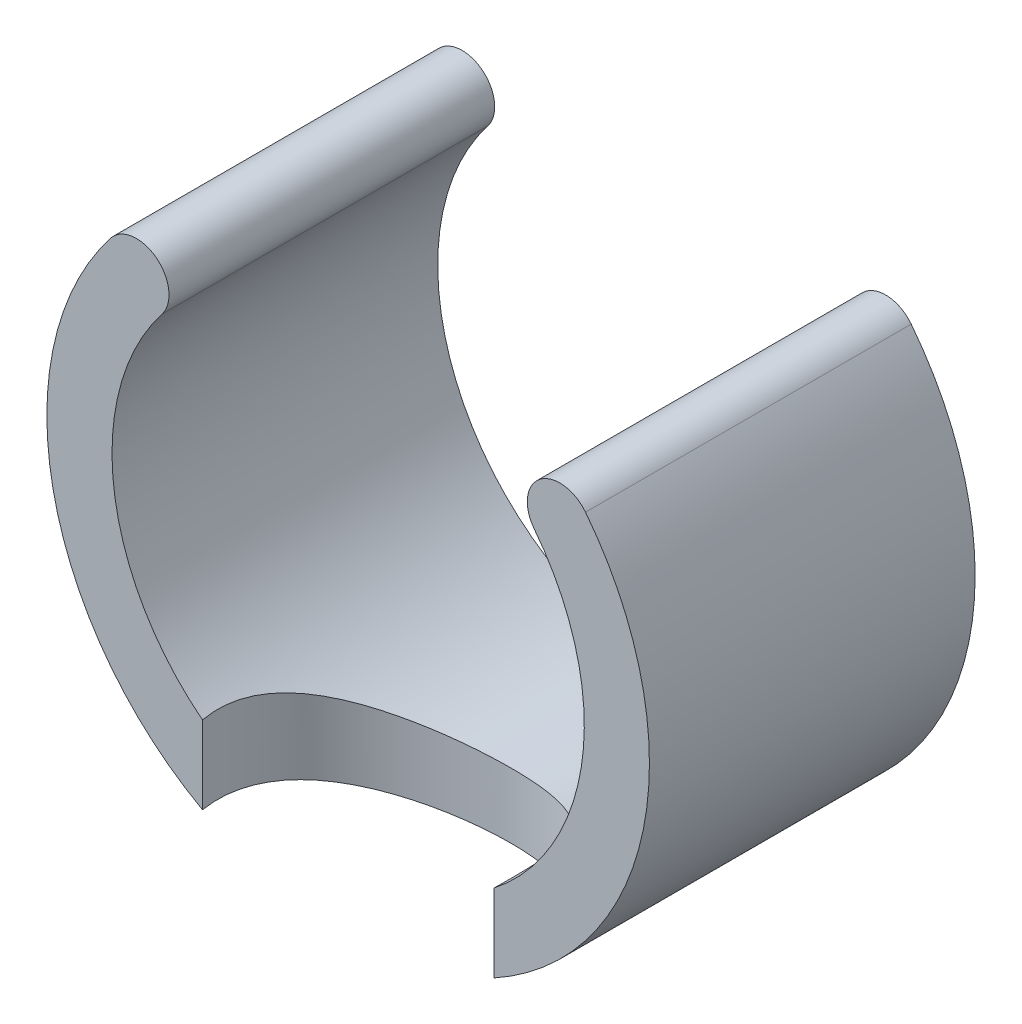
SolidWorks part; units mm, degrees
ref_plane "Спереди" through (0, 0, 0) normal (0, 0, 1) x (1, 0, 0)
ref_plane "Сверху" through (0, 0, 0) normal (0, 1, 0) x (1, 0, 0)
ref_plane "Справа" through (0, 0, 0) normal (1, 0, 0) x (0, 0, -1)
sketch "Эскиз1" plane through (0, 0, 0) normal (0, 0, 1) x (1, 0, 0)
  line L0 (0, -9.25) -> (0, 9.25) construction
  line L1 (-5.5, 5.0806) -> (-5.5, -4.3036) construction
  line L2 (5.5, 5.0806) -> (5.5, -4.3036) construction
  arc A0 (-5.7121, 4.4648) -> (5.7121, 4.4648) centre (0, 0) ccw
  arc A1 (-7.2879, 5.6964) -> (7.2879, 5.6964) centre (0, 0) ccw
  arc A2 (-7.2879, 5.6964) -> (-5.7121, 4.4648) centre (-6.5, 5.0806) cw
  arc A3 (7.2879, 5.6964) -> (5.7121, 4.4648) centre (6.5, 5.0806) ccw
  circle A5 centre (0, 0) radius 9.25 construction
  circle A6 centre (0, 0) radius 7.25 construction
  point P4 (6.9332, 2.1197)
  point P17 (8.8458, 2.7044)
  dimension "D1" = 14.5
  dimension "D3" = 11
  dimension "D2" = 2
extrude "Основа" add sketch "Эскиз1" along normal blind 10
sketch "Эскиз2" plane through (0, 0, 0) normal (1, 0, 0) x (0, 0, -1)
  line L0 (-5, -9.25) -> (-5, 7) construction
  line L1 (-10, -9.25) -> (0, -9.25) construction
  line L3 (0, -9.25) -> (0, 5.6964) construction
  line L4 (2, -5.25) -> (2, 6)
  line L5 (4, 6) -> (4, -5.25)
  line L6 (0, -9.25) -> (0, -7.25)
  line L7 (-10, -9.25) -> (0, -9.25) construction
  line L8 (-10, 5.6964) -> (-10, -9.25) construction
  arc A0 (2, -5.25) -> (0, -7.25) centre (0, -5.25) cw
  circle A1 centre (-5, 0) radius 7 construction
  arc A2 (4, -5.25) -> (0, -9.25) centre (0, -5.25) cw
  arc A3 (2.1323, -1.8657) -> (0, -9.25) centre (0, -5.25) cw construction
  arc A4 (2, 6) -> (4, 6) centre (3, 6) cw
  arc A5 (1.0661, -3.5579) -> (0, -7.25) centre (0, -5.25) cw construction
  point P29 (3, 7)
  dimension "D1" = 14
  dimension "D3" = 9.25
  dimension "D2" = 2
extrude "Бобышка-Вытянуть2" [suppressed] add sketch "Эскиз2" along normal blind 5 and the other way blind 5
sketch "Эскиз3" plane through (0, 0, 0) normal (0, 0, -1) x (-1, 0, 0)
  line L0 (-1.5, 7.0931) -> (-2.75, 0.004)
  line L1 (0, 7.25) -> (0, -9.25) construction
  line L2 (1.5, 7.0931) -> (2.75, 0.004)
  arc A0 (-6, -7.0401) -> (6, -7.0401) centre (0, 0) ccw
  arc A3 (-7.2879, 5.6964) -> (7.2879, 5.6964) centre (0, 0) ccw construction
  arc A4 (-2.75, 0.004) -> (-6, -7.0401) centre (-17.736, 2.6465) cw
  arc A5 (2.75, 0.004) -> (6, -7.0401) centre (17.736, 2.6465) ccw
  arc A6 (1.5, 7.0931) -> (-1.5, 7.0931) centre (0, 0) ccw
  arc A7 (-5.7121, 4.4648) -> (5.7121, 4.4648) centre (0, 0) ccw construction
  dimension "D1" = 10
  dimension "D2" = 3
  dimension "D3" = 12
  dimension "D4" = 5.5
extrude "упорчик снизу" [suppressed] add sketch "Эскиз3" along normal blind 2 from offset 1
fillet "Скругление1" [suppressed] radius 1
ref_plane "Плоскость1" through (0, -9.25, 0) normal (0, -1, 0) x (-1, 0, 0)
sketch "Эскиз5" plane through (0, 0, 10) normal (0, 0, 1) x (1, 0, 0)
  line L0 (0, 9.25) -> (0, -9.25) construction
  arc A1 (-5.0581, -5.194) -> (5.0581, -5.194) centre (0, 0) ccw
  arc A2 (-5.7121, 4.4648) -> (5.7121, 4.4648) centre (0, 0) ccw construction
  arc A3 (-7.5, -7.7015) -> (7.5, -7.7015) centre (0, 0) ccw
  arc A5 (-7.5, -7.7015) -> (-5.0581, -5.194) centre (-6.2791, -6.4477) cw
  arc A6 (7.5, -7.7015) -> (5.0581, -5.194) centre (6.2791, -6.4477) ccw
  dimension "D1" = 15
  dimension "D2" = 3.5
extrude "выступ под толкатель" [suppressed] add sketch "Эскиз5" along normal blind 6 and the other way blind 9
sketch "Эскиз6" plane through (0, -9.25, 0) normal (0, -1, 0) x (-1, 0, 0)
  circle A0 centre (0, -9.5) radius 4.5
  dimension "D1" = 9.5
  dimension "D2" = 9
extrude "Вырез под толкатель" cut sketch "Эскиз6" against normal through all and the other way through all
sketch "Эскиз7" [suppressed] plane through (0, 0, -3) normal (0, 0, -1) x (-1, 0, 0)
  line L0 (0, 0) -> (0, -9.25) construction
  line L1 (-7.0595, -8.8662) -> (-5.2044, -7.647)
  line L2 (-1.3246, -11.2557) -> (-1.7652, -9.08)
  line L3 (-5, -12) -> (-3.5577, -8.5385) construction
  line L4 (5, -12) -> (3.5577, -8.5385) construction
  line L5 (1.3246, -11.2557) -> (1.7652, -9.08)
  line L6 (7.0595, -8.8662) -> (5.2044, -7.647)
  arc A0 (-7.0595, -8.8662) -> (-1.3246, -11.2557) centre (-5, -12) ccw
  arc A1 (-5.2044, -7.647) -> (5.2044, -7.647) centre (0, 0) ccw construction
  circle A2 centre (-5, -12) radius 1.4
  arc A11 (-5.2044, -7.647) -> (-1.7652, -9.08) centre (0, 0) ccw
  arc A12 (5.2044, -7.647) -> (1.7652, -9.08) centre (0, 0) cw
  circle A13 centre (5, -12) radius 1.4
  arc A14 (7.0595, -8.8662) -> (1.3246, -11.2557) centre (5, -12) cw
  dimension "D1" = 7.5
  dimension "D2" = 2.8
  dimension "D3" = 5
extrude "Наплывы под шурупы для крепления куда-нибудь" [suppressed] add sketch "Эскиз7" against normal blind 2
chamfer "Фаска2" [suppressed] distance 1.5 angle 45
sketch "Эскиз8" [suppressed] plane through (0, 0, 0) normal (0, 0, -1) x (-1, 0, 0)
  line L1 (0, 0) -> (0, -9.25) construction
  arc A0 (-6, -7.0401) -> (6, -7.0401) centre (0, 0) ccw
  arc A1 (-4.8265, -5.41) -> (4.8265, -5.41) centre (0, 0) ccw
  arc A2 (-5.7121, 4.4648) -> (5.7121, 4.4648) centre (0, 0) ccw construction
  arc A3 (-7.2879, 5.6964) -> (7.2879, 5.6964) centre (0, 0) ccw construction
  arc A5 (-6, -7.0401) -> (-4.8265, -5.41) centre (-17.736, 2.6465) ccw
  arc A6 (-6, -7.0401) -> (-2.75, 0.004) centre (-17.736, 2.6465) ccw construction
  arc A7 (6, -7.0401) -> (4.8265, -5.41) centre (17.736, 2.6465) cw
extrude "Выступ между основой и нижним упором" [suppressed] add sketch "Эскиз8" along normal up to surface (1 mm away)
chamfer "Фаска3" [suppressed] distance 1.5 angle 45
chamfer "Фаска4" [suppressed] distance 4.5 distance2 0.5
